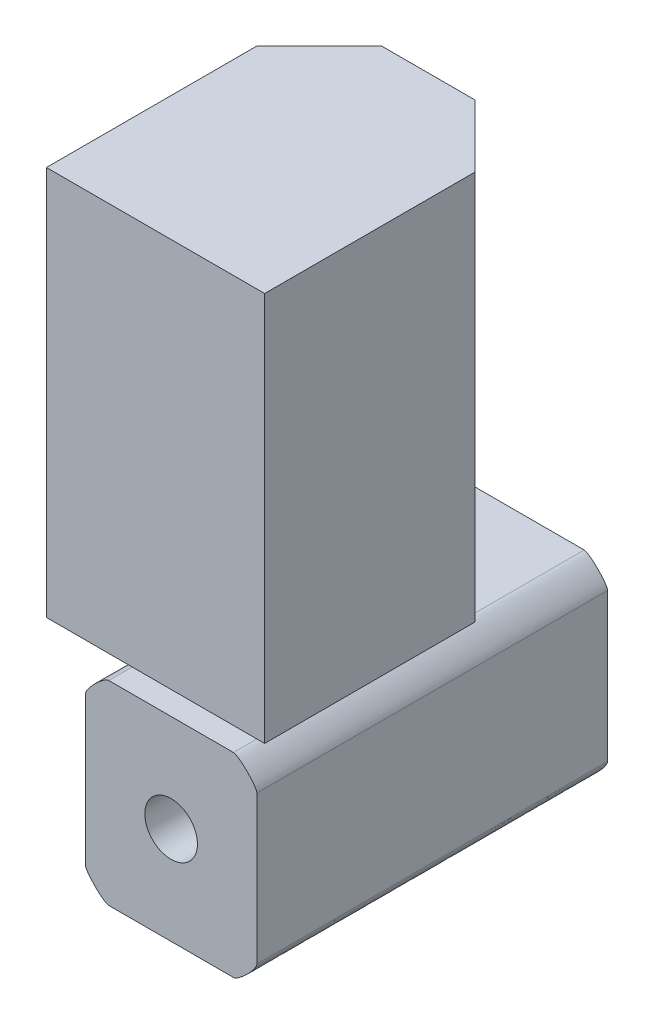
SolidWorks part; units mm, degrees
ref_plane "Plan de face" through (0, 0, 0) normal (0, 0, 1) x (1, 0, 0)
ref_plane "Plan de dessus" through (0, 0, 0) normal (0, 1, 0) x (1, 0, 0)
ref_plane "Plan de droite" through (0, 0, 0) normal (1, 0, 0) x (0, 0, -1)
sketch "Esquisse1" plane through (0, 0, 0) normal (0, 0, 1) x (1, 0, 0)
  line L0 (-88.8215, 29.1571) -> (-66.8215, 4.1571) construction
  line L1 (-88.8215, 29.1571) -> (-66.8215, 29.1571)
  line L2 (-88.8215, 29.1571) -> (-88.8215, 4.1571)
  line L3 (-88.8215, 4.1571) -> (-66.8215, 4.1571)
  line L4 (-66.8215, 29.1571) -> (-66.8215, 4.1571)
  line L5 (-88.8215, 4.1571) -> (-66.8215, 29.1571) construction
  point P4 (-77.8215, 16.6571)
  dimension "D1" = 25
  dimension "D2" = 22
extrude "Boss.-Extru.1" add sketch "Esquisse1" along normal blind 45 contours L4 L3 L2 L1
sketch "Esquisse2" plane through (0, 29.1571, 0) normal (0, 1, 0) x (1, 0, 0)
  line L0 (-88.8215, 0) -> (-66.8215, -45) construction
  line L1 (-88.8215, 0) -> (-66.8215, 0) construction
  line L2 (-66.8215, -45) -> (-66.8215, 0) construction
  line L3 (-66.8215, -45) -> (-66.8215, 0) construction
  line L4 (-66.8215, 0) -> (-88.8215, -45) construction
  line L6 (-85.3215, -18.1699) -> (-85.3215, -26.8301)
  line L7 (-85.3215, -26.8301) -> (-77.8215, -31.1603)
  line L8 (-77.8215, -31.1603) -> (-70.3215, -26.8301)
  line L9 (-70.3215, -26.8301) -> (-70.3215, -18.1699)
  line L10 (-70.3215, -18.1699) -> (-77.8215, -13.8397)
  line L11 (-77.8215, -13.8397) -> (-85.3215, -18.1699)
  line L12 (-88.8215, -45) -> (-88.8215, 0) construction
  circle A0 centre (-77.8215, -22.5) radius 7.5 construction
  point P5 (-77.8215, -22.5)
  dimension "D1" = 15
extrude "Boss.-Extru.2" add sketch "Esquisse2" along normal blind 5
sketch "Esquisse4" plane through (0, 34.1571, 0) normal (0, 1, 0) x (1, 0, 0)
  line L1 (-83.8215, -12) -> (-71.8215, -12)
  line L2 (-91.8215, -20) -> (-91.8215, -47)
  line L3 (-91.8215, -47) -> (-63.8215, -47)
  line L4 (-63.8215, -20) -> (-63.8215, -47)
  line L5 (-88.8215, -45) -> (-66.8215, -45) construction
  line L6 (-91.8215, -20) -> (-83.8215, -12)
  line L7 (-83.8215, -12) -> (-71.8215, -12)
  line L8 (-71.8215, -12) -> (-63.8215, -20)
  point P11 (0, 0)
  point P12 (0, 0)
  point P13 (-91.8215, -19.6877)
  line M5 (-77.8215, -13.8397) -> (-85.3215, -18.1699)
  line M6 (-85.3215, -18.1699) -> (-85.3215, -26.8301)
  line M7 (-85.3215, -26.8301) -> (-77.8215, -31.1603)
  line M8 (-77.8215, -31.1603) -> (-70.3215, -26.8301)
  line M9 (-70.3215, -26.8301) -> (-70.3215, -18.1699)
  line M10 (-70.3215, -18.1699) -> (-77.8215, -13.8397)
  dimension "D3" = 14
  dimension "D4" = 2
  dimension "D7" = 8
extrude "Boss.-Extru.3" add sketch "Esquisse4" along normal blind 50 contours M10 M5 M6 M7 M8 M9 | L8 L1 L6 L2 L3 L4 M5 M10 M9 M8 M7 M6 region at (-77.8215, 34.1571, 32.7079) region at (-77.8215, 34.1571, 22.5)
hole_wizard "Dégagement 1/41" positions "Esquisse7" profile "Esquisse8" hole size "1/4" standard "Ansi Inch" end condition up to next
sketch "Esquisse7" plane through (0, 0, 0) normal (0, 0, -1) x (-1, 0, 0)
  point P0 (77.8215, 16.6571)
sketch "Esquisse8" plane through (-77.8215, 16.6571, 0) normal (1, 0, 0) x (0, 1, 0)
  line L0 (0, 0) -> (0, 45)
  line L1 (0, 45) -> (3.3782, 45)
  line L2 (3.3782, 45) -> (3.3782, 0.635)
  line L3 (3.3782, 0.635) -> (4.0132, 0)
  line L5 (4.0132, 0) -> (0, 0)
  line L6 (-3.3782, 0.635) -> (-4.0132, 0) construction
  line L11 (0, -6.35) -> (0, 107.95) construction
  dimension "Diamètre du perçage jusqu'au prochain" = 6.7564
  dimension "Profondeur du perçage jusqu'au prochain" = 45
  dimension "Diamètre du fraisage entrant" = 8.0264
  dimension "Angle du fraisage entrant" = 90
fillet "Congé1" radius 3 4 edges at (-88.8215, 4.1571, 22.5) (-88.8215, 29.1571, 22.5) (-66.8215, 29.1571, 22.5) (-66.8215, 4.1571, 22.5) conic radius 10
